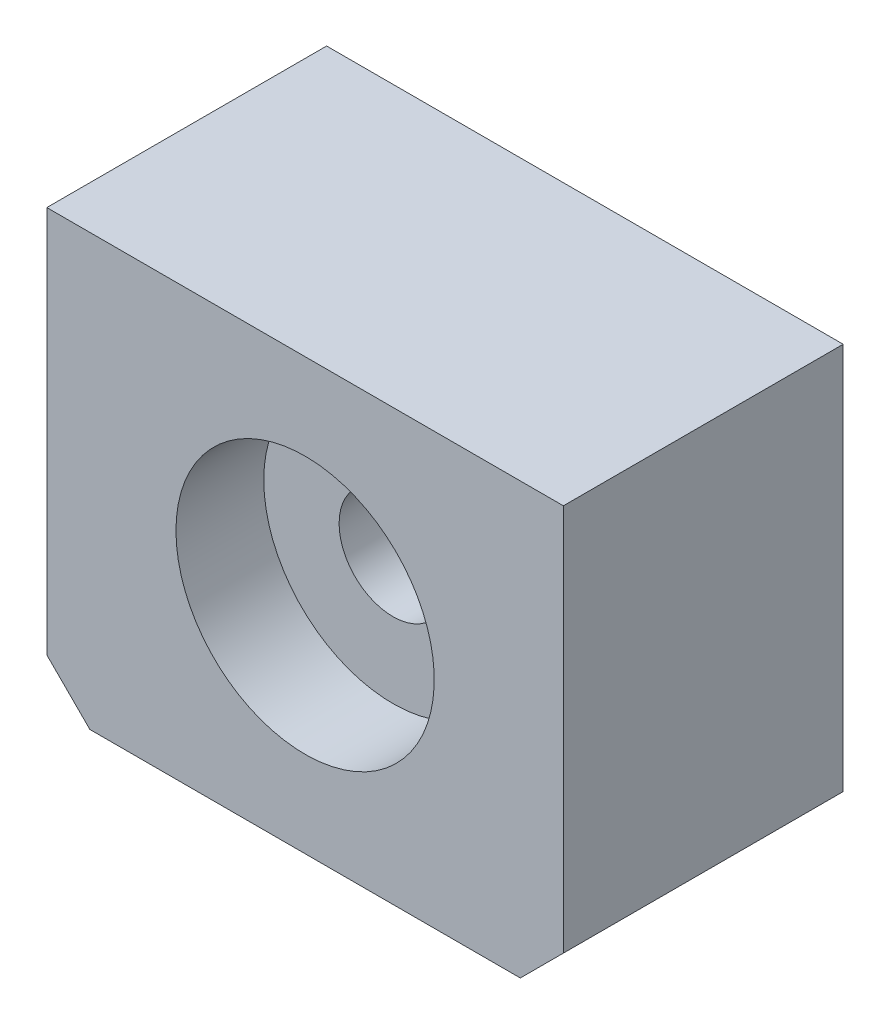
SolidWorks part; units mm, degrees
ref_plane "Front" through (0, 0, 0) normal (0, 0, 1) x (1, 0, 0)
ref_plane "Top" through (0, 0, 0) normal (0, 1, 0) x (1, 0, 0)
ref_plane "Right" through (0, 0, 0) normal (1, 0, 0) x (0, 0, -1)
sketch "Sketch1" plane through (0, 0, 0) normal (0, 0, 1) x (1, 0, 0)
  line L1 (19.05, -15.875) -> (-19.05, -15.875)
  line L2 (19.05, -15.875) -> (19.05, 15.875)
  line L3 (19.05, 15.875) -> (-19.05, 15.875)
  line L4 (-19.05, -15.875) -> (-19.05, 15.875)
  line L5 (19.05, -15.875) -> (-19.05, 15.875) construction
  line L6 (19.05, 15.875) -> (-19.05, -15.875) construction
  point P0 (0, 0)
  dimension "D1" = 31.75
  dimension "D2" = 38.1
extrude "Boss-Extrude1" add sketch "Sketch1" along normal blind 20.6375
sketch "Sketch2" plane through (0, 0, 0) normal (0, 0, -1) x (-1, 0, 0)
  circle A0 centre (0, 0) radius 11.1125
  dimension "D1" = 22.225
extrude "Cut-Extrude1" cut sketch "Sketch2" against normal blind 6.985
sketch "Sketch3" plane through (0, 0, 6.985) normal (0, 0, -1) x (-1, 0, 0)
  circle A0 centre (0, 0) radius 8.255
  dimension "D1" = 16.51
extrude "Cut-Extrude2" cut sketch "Sketch3" against normal blind 2.413
sketch "Sketch4" plane through (0, 0, 9.398) normal (0, 0, -1) x (-1, 0, 0)
  circle A0 centre (0, 0) radius 3.9688
  dimension "D1" = 7.9375
extrude "Cut-Extrude3" cut sketch "Sketch4" against normal through all
sketch "Sketch6" plane through (0, 0, 9.398) normal (0, 0, -1) x (-1, 0, 0)
  circle A0 centre (0, 0) radius 9.525
  dimension "D1" = 19.05
extrude "Cut-Extrude4" cut sketch "Sketch6" against normal through all from offset 4.7625 offset against normal yes
chamfer "Chamfer1" distance 3.175 angle 45 2 edges at (19.05, -15.875, 10.3187) (-19.05, -15.875, 10.3187)
hole_wizard "#4 Clearance Hole1" positions "Sketch7" profile "Sketch8" hole size "#4" standard "ANSI Inch"
sketch "Sketch7" plane through (-19.05, -28.277, 98.8948) normal (-1, 0, 0) x (0, 0, 1)
  point P0 (-92.5448, 31.452)
  point P1 (-83.0198, 31.452)
  point P2 (-83.0198, 21.927)
  point P3 (-92.5448, 21.927)
  point P6 (0, 0)
  point P7 (0, 0)
  point P8 (0, 0)
  point P9 (0, 0)
sketch "Sketch8" plane through (-19.05, 3.175, 6.35) normal (0, 1, 0) x (0, 0, 1)
  line L0 (0, 0) -> (0, 6.35)
  line L1 (0, 6.35) -> (1.6319, 6.35)
  line L2 (1.6319, 6.35) -> (1.6319, 0)
  line L3 (1.6319, 0) -> (0, 0)
  line L4 (0, -6.35) -> (0, 107.95) construction
  dimension "Thru Hole Dia." = 3.2639
  dimension "Thru Hole Depth" = 6.35
